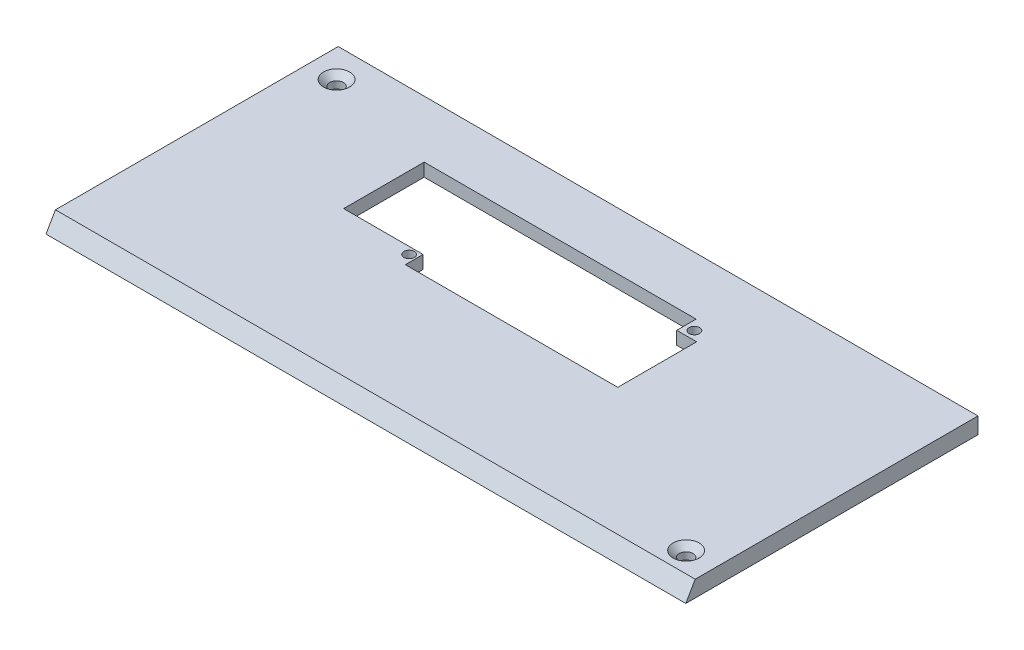
SolidWorks part; units mm, degrees
ref_plane "Alzado" through (0, 0, 0) normal (0, 0, 1) x (1, 0, 0)
ref_plane "Planta" through (0, 0, 0) normal (0, 1, 0) x (1, 0, 0)
ref_plane "Vista lateral" through (0, 0, 0) normal (1, 0, 0) x (0, 0, -1)
sketch "Croquis1" plane through (0, 0, 0) normal (1, 0, 0) x (0, 0, -1)
  line L0 (0, 0) -> (89.52, 0)
  line L1 (89.52, 0) -> (89.52, 5)
  line L2 (89.52, 5) -> (2.8868, 5)
  line L3 (0, 0) -> (2.8868, 5)
  dimension "D1" = 89.52
  dimension "D2" = 5
  dimension "D3" = 120
extrude "Saliente-Extruir1" add sketch "Croquis1" along normal blind 196
shell "Vaciado1" thickness 4 removed face at (98, 0, -44.76)
sketch "Sketch1" plane through (0, 1, 0) normal (0, -1, 0) x (-1, 0, 0)
  line L0 (0, 89.52) -> (-196, 89.52) construction
  line L1 (-98, 89.52) -> (-98, -14.2345)
sketch "Sketch2" plane through (0, 1, 0) normal (0, -1, 0) x (-1, 0, 0)
  line L0 (-59.6372, 47.3551) -> (-68.1615, 47.3551)
  line L5 (-68.1615, 47.3551) -> (-68.1615, 41.923)
  line L6 (-68.1615, 41.923) -> (-133.2369, 41.923)
  line L7 (-133.2369, 41.923) -> (-133.2369, 66.0933)
  line L8 (-133.2369, 66.0933) -> (-127.1352, 66.0933)
  line L9 (-127.1352, 66.0933) -> (-127.1352, 72.023)
  line L10 (-127.1352, 72.023) -> (-59.6372, 72.023)
  line L11 (-59.6372, 72.023) -> (-59.6372, 47.3551)
  circle A0 centre (-66.0169, 45.223) radius 1.6
  circle A1 centre (-129.9169, 68.723) radius 1.6
  point P4 (-97.9669, 56.973)
extrude "Cut-Extrude1" cut sketch "Sketch2" against normal blind 4.9
sketch "Sketch3" plane through (0, 5, 0) normal (0, 1, 0) x (1, 0, 0)
  line L0 (59.6372, 72.023) -> (42.4477, 72.023) construction
  line L1 (42.4477, 72.023) -> (42.4477, 47.3551) construction
  line L2 (42.4477, 47.3551) -> (59.6372, 47.3551) construction
  line L3 (59.6372, 47.3551) -> (59.6372, 72.023) construction
  line L4 (59.6372, 47.3551) -> (43.829, 47.3551)
  line L5 (59.6372, 47.3551) -> (59.6372, 72.023)
  line L6 (59.6372, 72.023) -> (43.829, 72.023)
  line L7 (43.829, 47.3551) -> (43.829, 72.023)
  line L8 (59.6372, 47.3551) -> (43.829, 72.023) construction
  line L9 (59.6372, 72.023) -> (43.829, 47.3551) construction
  point P8 (43.1384, 59.6891)
extrude "Cut-Extrude2" cut sketch "Sketch3" against normal blind 10
sketch "Sketch4" plane through (0, 1, 0) normal (0, -1, 0) x (-1, 0, 0)
  circle A0 centre (-8.5, 80.52) radius 1.585
  circle A1 centre (-187, 9.1109) radius 1.585
extrude "Cut-Extrude3" cut sketch "Sketch4" against normal blind 13
hole_wizard "Avellanado para tornillo con cabeza avellanada en cruz de M3.51" positions "3DSketch1" profile "Sketch5" countersink size "M3.5" standard "AS"
sketch3d "3DSketch1"
  line L0 (187, 5, -9.1109) -> (187, 1, -9.1109) construction
  line L1 (8.5, 5, -80.52) -> (8.5, 1, -80.52) construction
  point P0 (187, 5, -9.1109)
  point P4 (8.5, 5, -80.52)
sketch "Sketch5" plane through (187, 5, -9.1109) normal (1, 0, 0) x (0, 0, 1)
  line L0 (0, 0) -> (0, 11.2618)
  line L1 (0, 11.2618) -> (2.1, 10)
  line L2 (2.1, 10) -> (2.1, 1.8348)
  line L3 (2.1, 1.8348) -> (4, 0)
  line L5 (4, 0) -> (0, 0)
  line L6 (-2.1, 1.8348) -> (-4, 0) construction
  line L10 (0, 11.2618) -> (-2.1, 10) construction
  line L11 (0, -6.35) -> (0, 107.95) construction
  dimension "Diámetro de taladro" = 4.2
  dimension "Profundidad de taladro" = 10
  dimension "Ángulo de avellanado cercano" = 8
  dimension "Ángulo de avellanado lejano" = 92
  dimension "Ángulo de perforador" = 118
